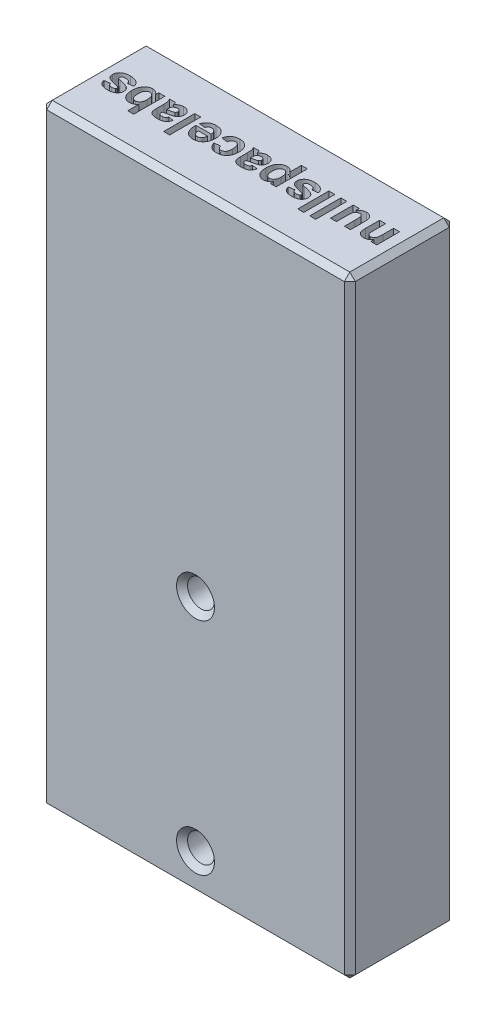
SolidWorks part; units mm, degrees
ref_plane "Front Plane" through (0, 0, 0) normal (0, 0, 1) x (1, 0, 0)
ref_plane "Top Plane" through (0, 0, 0) normal (0, 1, 0) x (1, 0, 0)
ref_plane "Right Plane" through (0, 0, 0) normal (1, 0, 0) x (0, 0, -1)
sketch "Sketch1" plane through (0, 0, 0) normal (0, 0, 1) x (1, 0, 0)
  line L1 (0, 0) -> (28, 0)
  line L2 (0, 0) -> (0, 55.475)
  line L3 (0, 55.475) -> (28, 55.475)
  line L4 (28, 0) -> (28, 55.475)
  dimension "D1" = 28
  dimension "D2" = 55.475
extrude "Boss-Extrude1" add sketch "Sketch1" along normal blind 9.525
sketch "Sketch2" plane through (0, 0, 0) normal (0, -1, 0) x (1, 0, 0)
  line L0 (0, 0) -> (28, 0) construction
  line L1 (0, 9.525) -> (0, 0) construction
  circle A0 centre (5, 4.7625) radius 1.2195
  circle A3 centre (23, 4.7625) radius 1.2195
  dimension "D1" = 2.439
  dimension "D6" = 2.439
  dimension "D2" = 4.7625
  dimension "D3" = 5
  dimension "D4" = 18
extrude "Cut-Extrude1" cut sketch "Sketch2" against normal blind 20
sketch "Sketch3" plane through (0, 0, 9.525) normal (0, 0, 1) x (1, 0, 0)
  line L0 (22.85, 65) -> (5.15, 65)
  line L1 (5.15, 65) -> (5.15, 0)
  line L2 (5.15, 0) -> (22.85, 0)
  line L3 (22.85, 0) -> (22.85, 65)
  line L4 (0, 55.475) -> (0, 0) construction
  circle A0 centre (14, 3.475) radius 1.7
  circle A1 centre (14, 3.475) radius 1.2195
  circle A2 centre (14, 23.475) radius 1.7
  circle A3 centre (14, 23.475) radius 1.2195
  dimension "D6" = 2.439
  dimension "D7" = 3.4
  dimension "D8" = 3.4
  dimension "D9" = 2.439
  dimension "D1" = 3.475
  dimension "D2" = 23.475
  dimension "D3" = 8.85
  dimension "D4" = 65
  dimension "D5" = 17.7
  dimension "D10" = 0
  dimension "D11" = 14
extrude "Cut-Extrude2" cut sketch "Sketch3" against normal through all contours A3 | A1 region at (14, 3.475, 9.525) region at (14, 23.475, 9.525)
chamfer "Chamfer1" distance 0.5 angle 45 12 edges at (14, 0, 0) (28, 0, 4.7625) (28, 27.7375, 0) (14, 55.475, 0) (28, 55.475, 4.7625) (28, 27.7375, 9.525) (14, 55.475, 9.525) (14, 0, 9.525) (0, 0, 4.7625) (0, 27.7375, 0) (0, 55.475, 4.7625) (0, 27.7375, 9.525)
chamfer "Chamfer2" distance 0.5 angle 45 6 edges at (23, 0, 3.543) (5, 0, 3.543) (15.2195, 3.475, 0) (15.2195, 23.475, 0) (15.2195, 3.475, 9.525) (15.2195, 23.475, 9.525)
sketch "Sketch4" plane through (0, 55.475, 0) normal (0, 1, 0) x (-1, 0, 0)
  text T0 "nullspacelabs" font "Arial" height in points 11
extrude "Cut-Extrude3" cut sketch "Sketch4" against normal blind 1.5875
